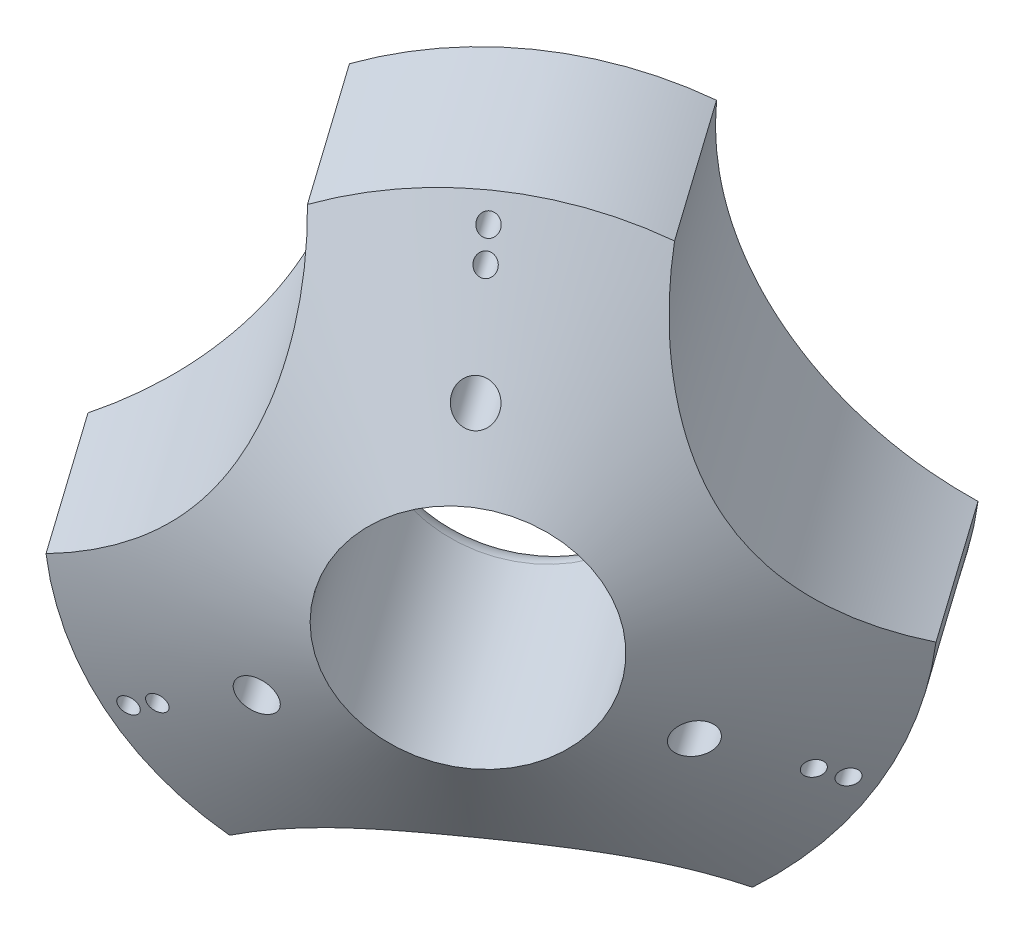
SolidWorks part; units mm, degrees
material "ABS"
ref_plane "前视基准面" through (0, 0, 0) normal (0, 0, 1) x (1, 0, 0)
ref_plane "上视基准面" through (0, 0, 0) normal (0, 1, 0) x (1, 0, 0)
ref_plane "右视基准面" through (0, 0, 0) normal (1, 0, 0) x (0, 0, -1)
other "Configuration Table"
sketch "草图1" plane through (0, 0, 0) normal (0, 1, 0) x (1, 0, 0)
  line L0 (0, 0) -> (50000, 0) construction
  line L1 (0, 0) -> (43301.2702, 25000) construction
  line L2 (0, 0) -> (25000, 43301.2702) construction
  line L3 (0, 0) -> (0, 50000) construction
  line L4 (0, 0) -> (-25000, 43301.2702) construction
  line L5 (0, 0) -> (-43301.2702, 25000) construction
  line L6 (-19.2134, -33.2787) -> (-30.3426, -17.5183)
  line L7 (-30.3426, -17.5183) -> (-61.1307, -35.2938)
  line L8 (-61.1307, -35.2938) -> (-38.709, -67.046)
  line L9 (-38.709, -67.046) -> (-19.2134, -33.2787)
  line L10 (-53.3699, -46.2842) -> (-45.2012, -40.516) construction
  line L11 (-45.2012, -40.516) -> (-33.2023, -57.5081)
  line L12 (-45.2012, -40.516) -> (-52.4343, -30.2729)
  spline S0 degree 4 poles (4.5441, -13.9852) (5.069, -13.9115) (6.1117, -13.7144) (7.5966, -13.2868) (9.4525, -12.4738) (11.1485, -11.4611) (12.673, -10.2854) (14.0902, -8.9027) (15.2006, -7.528) (16.0517, -6.2294) (16.6357, -5.1571) (16.9969, -4.4036) (17.2795, -3.7437) (17.4701, -3.2541) (17.647, -2.7595) (17.7869, -2.3315) (17.8956, -1.9726) (17.9965, -1.6106) (18.0724, -1.3201) (18.1431, -1.0312) (18.201, -0.7763) (18.2495, -0.5466) (18.2961, -0.3139) (18.338, -0.0934) (18.3688, 0.0809) (18.404, 0.2961) (18.438, 0.517) (18.4698, 0.7375) (18.5019, 0.9839) (18.5336, 1.2626) (18.5616, 1.5443) (18.5855, 1.8273) (18.6051, 2.1103) (18.6204, 2.3933) (18.6344, 2.7473) (18.6427, 3.1726) (18.6402, 3.6687) (18.606, 4.6606) (18.4743, 6.0736) (18.1443, 7.891) (17.4882, 10.0676) (16.5951, 12.1579) (15.4804, 14.1385) (14.1536, 15.9992) (12.6297, 17.7192) (10.7951, 19.3989) (8.6272, 20.9716) (6.1287, 22.3558) (3.3088, 23.4722) (0.3713, 24.2251) (-2.6362, 24.611) (-5.6679, 24.6319) (-8.6804, 24.2953) (-11.6337, 23.6131) (-14.4905, 22.6011) (-17.8988, 20.9477) (-21.6682, 18.3857) (-25.4815, 14.66) (-28.8831, 9.6089) (-31.2279, 3.9916) (-32.5355, -2.3024) (-32.5832, -9.4982) (-30.886, -17.2942) (-27.0418, -25.1548) (-21.1423, -32.1629) (-13.78, -37.6027) (-5.394, -41.2569) (3.5764, -43.0207) (12.7127, -42.8868) (21.6333, -40.9289) (30.0036, -37.2857) (37.5425, -32.1439) (44.0239, -25.7248) (49.277, -18.2707) (53.1837, -10.0336) (55.6749, -1.2666) (56.7255, 7.7843) (56.3496, 16.8863) (54.5948, 25.8236) (51.5367, 34.4007) (47.2736, 42.4454) (41.6252, 50.2164) (33.2939, 58.6988) (21.6024, 66.7973) (6.2316, 72.9489) (-11.9297, 75.3897) (-30.1426, 73.5037) (-47.4501, 67.5662) (-63.0493, 58.0235) (-76.3038, 45.4399) (-86.7456, 30.4509) (-94.067, 13.7235) (-98.1075, -4.0757) (-98.837, -22.3066) (-96.337, -40.374) (-90.7813, -57.7411) (-82.4178, -73.9383) (-71.5503, -88.568) (-58.5225, -101.306) (-43.7037, -111.9004) (-27.476, -120.169) (-10.2235, -125.9948) (7.6766, -129.3207) (25.8616, -130.1437) (43.989, -128.5088) (59.522, -125.003) (72.4202, -120.5917) (82.8104, -116.0253) (90.8771, -111.8583) (98.6697, -107.1992) (106.1617, -102.071) (114.2246, -95.801) (122.6763, -88.2215) (131.2888, -79.1727) (139.0767, -69.4058) (144.8157, -60.9536) (149.48, -53.1674) (153.2371, -46.1706) (156.1751, -40.0285) (158.8259, -33.7588) (160.8418, -28.4575) (162.3378, -24.1741) (163.5443, -20.3917) (164.5049, -17.1274) (165.2564, -14.393) (165.828, -12.1982) (166.3703, -9.9944) (166.8184, -8.0627) (167.1848, -6.398) (167.4765, -5.0161) (167.7053, -3.8925) (167.892, -2.9476) (168.0629, -2.0497) (168.1956, -1.3461) (168.4043, -0.1916) (168.4882, 0.2863) (168.6688, 1.3366) (168.7622, 1.9047) (168.8711, 2.5704) (169.0198, 3.5044) (169.1948, 4.6573) (169.389, 6.0027) (169.5701, 7.3351) (169.7422, 8.6768) (169.9433, 10.3507) (170.1641, 12.3645) (170.391, 14.7154) (170.6086, 17.4069) (170.7844, 20.1009) (170.9186, 22.7976) (171.0111, 25.4959) (171.0621, 28.1953) (171.0718, 30.8952) (171.0401, 33.595) (170.9491, 36.9686) (170.6302, 43.7113) (169.6923, 53.7988) (167.722, 65.8035) (165.138, 76.2991) (163.208, 82.7681) (162.3863, 85.3399) knots 0 0 0 0 0 0.002183 0.004365 0.006343 0.00832 0.010298 0.012275 0.014479 0.01558 0.016682 0.0173 0.017918 0.018536 0.018845 0.019463 0.019772 0.020081 0.02039 0.020699 0.021008 0.021162 0.021317 0.021626 0.021918 0.022064 0.02221 0.022501 0.022793 0.023085 0.023377 0.023669 0.023961 0.024253 0.024544 0.025128 0.025712 0.026296 0.028631 0.030966 0.033302 0.035637 0.037972 0.040307 0.042695 0.045083 0.048197 0.05131 0.054424 0.057538 0.060652 0.063766 0.066879 0.069993 0.073107 0.07622 0.082448 0.088676 0.094903 0.10113 0.107357 0.114993 0.124334 0.133675 0.143016 0.152357 0.161699 0.17104 0.18038 0.189722 0.199063 0.208404 0.217745 0.227086 0.236427 0.245769 0.25511 0.264451 0.273792 0.283133 0.292474 0.301815 0.313225 0.331907 0.35059 0.369272 0.387954 0.406636 0.425318 0.444001 0.462683 0.481365 0.500047 0.518729 0.537412 0.556094 0.574776 0.593458 0.612141 0.630823 0.649505 0.668187 0.68687 0.705552 0.724234 0.742916 0.752258 0.761599 0.77094 0.780281 0.789622 0.798963 0.812975 0.826987 0.840998 0.85034 0.85501 0.864351 0.873692 0.878363 0.883033 0.887704 0.892374 0.89471 0.897045 0.89938 0.901716 0.904051 0.905219 0.906387 0.907554 0.908722 0.909306 0.90989 0.911057 0.912447 0.912794 0.913142 0.913837 0.915226 0.916616 0.918006 0.919396 0.920785 0.922175 0.924955 0.927734 0.930513 0.933293 0.936072 0.938852 0.941631 0.944411 0.94719 0.94997 0.955529 0.972205 0.988882 1 1 1 1 1 construction
  spline S1 degree 4 poles (18.3541, 0) (18.3651, 0.0621) (18.381, 0.1554) (18.404, 0.2961) (18.438, 0.517) (18.4698, 0.7375) (18.5019, 0.9839) (18.5336, 1.2626) (18.5616, 1.5443) (18.5855, 1.8273) (18.6051, 2.1103) (18.6204, 2.3933) (18.6344, 2.7473) (18.6427, 3.1726) (18.6402, 3.6687) (18.606, 4.6606) (18.4743, 6.0736) (18.1443, 7.891) (17.4882, 10.0676) (16.5951, 12.1579) (15.4804, 14.1385) (14.1536, 15.9992) (12.6297, 17.7192) (10.7951, 19.3989) (8.6272, 20.9716) (6.1287, 22.3558) (3.3088, 23.4722) (0.3713, 24.2251) (-2.6362, 24.611) (-5.6679, 24.6319) (-8.6804, 24.2953) (-11.6337, 23.6131) (-14.4905, 22.6011) (-17.8988, 20.9477) (-21.6682, 18.3857) (-25.4815, 14.66) (-28.8831, 9.6089) (-31.2279, 3.9916) (-32.5355, -2.3024) (-32.5832, -9.4982) (-30.886, -17.2942) (-27.0418, -25.1548) (-21.1423, -32.1629) (-13.78, -37.6027) (-5.394, -41.2569) (3.5764, -43.0207) (12.7127, -42.8868) (21.6333, -40.9289) (30.0036, -37.2857) (37.5425, -32.1439) (44.0239, -25.7248) (49.277, -18.2707) (53.1837, -10.0336) (55.6749, -1.2666) (56.7255, 7.7843) (56.3496, 16.8863) (54.5948, 25.8236) (51.5367, 34.4007) (47.2736, 42.4454) (41.6252, 50.2164) (33.2939, 58.6988) (21.6024, 66.7973) (6.2316, 72.9489) (-11.9297, 75.3897) (-30.1426, 73.5037) (-47.4501, 67.5662) (-63.0493, 58.0235) (-76.3038, 45.4399) (-86.7456, 30.4509) (-94.067, 13.7235) (-98.1075, -4.0757) (-98.837, -22.3066) (-96.337, -40.374) (-90.7813, -57.7411) (-82.4178, -73.9383) (-71.5503, -88.568) (-58.5225, -101.306) (-43.7037, -111.9004) (-27.476, -120.169) (-10.2235, -125.9948) (7.6766, -129.3207) (25.8616, -130.1437) (43.989, -128.5088) (59.522, -125.003) (72.4202, -120.5917) (82.8104, -116.0253) (90.8771, -111.8583) (98.6697, -107.1992) (106.1617, -102.071) (114.2246, -95.801) (122.6763, -88.2215) (131.2888, -79.1727) (139.0767, -69.4058) (144.8157, -60.9536) (149.48, -53.1674) (153.2371, -46.1706) (156.1751, -40.0285) (158.8259, -33.7588) (160.8418, -28.4575) (162.3378, -24.1741) (163.5443, -20.3917) (164.5049, -17.1274) (165.2564, -14.393) (165.828, -12.1982) (166.3703, -9.9944) (166.8184, -8.0627) (167.1848, -6.398) (167.4765, -5.0161) (167.7053, -3.8925) (167.892, -2.9476) (168.0629, -2.0497) (168.1956, -1.3461) (168.3264, -0.6223) (168.3933, -0.2484) (168.4372, 0) knots 0.021626 0.021626 0.021626 0.021626 0.021626 0.021918 0.022064 0.02221 0.022501 0.022793 0.023085 0.023377 0.023669 0.023961 0.024253 0.024544 0.025128 0.025712 0.026296 0.028631 0.030966 0.033302 0.035637 0.037972 0.040307 0.042695 0.045083 0.048197 0.05131 0.054424 0.057538 0.060652 0.063766 0.066879 0.069993 0.073107 0.07622 0.082448 0.088676 0.094903 0.10113 0.107357 0.114993 0.124334 0.133675 0.143016 0.152357 0.161699 0.17104 0.18038 0.189722 0.199063 0.208404 0.217745 0.227086 0.236427 0.245769 0.25511 0.264451 0.273792 0.283133 0.292474 0.301815 0.313225 0.331907 0.35059 0.369272 0.387954 0.406636 0.425318 0.444001 0.462683 0.481365 0.500047 0.518729 0.537412 0.556094 0.574776 0.593458 0.612141 0.630823 0.649505 0.668187 0.68687 0.705552 0.724234 0.742916 0.752258 0.761599 0.77094 0.780281 0.789622 0.798963 0.812975 0.826987 0.840998 0.85034 0.85501 0.864351 0.873692 0.878363 0.883033 0.887704 0.892374 0.89471 0.897045 0.89938 0.901716 0.904051 0.905219 0.906387 0.907554 0.908722 0.909306 0.90989 0.911057 0.911057 0.911057 0.911057 0.911057
  spline S2 degree 4 poles (26.7771, -19.4547) (27.2791, -18.9699) (28.2564, -17.9726) (29.6389, -16.3972) (31.5138, -13.8737) (32.9647, -11.4834) (34.0651, -9.2997) (34.8847, -7.3726) (35.3191, -6.2309) (35.6599, -5.2409) (35.9229, -4.4091) (36.0959, -3.8235) (36.2363, -3.3192) (36.3702, -2.8132) (36.4765, -2.3905) (36.5777, -1.9654) (36.6735, -1.5395) (36.7371, -1.2443) (36.7899, -0.9895) (36.8338, -0.7701) (36.8689, -0.5895) (36.9122, -0.3614) (36.9643, -0.079) (37.0022, 0.137) (37.056, 0.4587) (37.1012, 0.7414) (37.1347, 0.96) (37.1737, 1.2255) (37.2176, 1.5413) (37.2661, 1.9157) (37.3168, 2.3441) (37.3624, 2.7721) (37.4134, 3.3079) (37.4649, 3.9519) (37.524, 4.9191) (37.5642, 6.2107) (37.5499, 8.58) (37.2749, 12.0191) (36.4953, 16.2666) (34.9181, 21.2024) (32.7382, 25.9024) (30.2297, 29.9345) (27.5748, 33.3344) (24.3272, 36.7897) (20.4102, 40.1789) (15.3713, 43.5302) (9.113, 46.471) (2.4988, 48.4837) (-3.4771, 49.4179) (-8.6498, 49.6296) (-15.5372, 49.2939) (-22.3494, 48.0444) (-29.7217, 45.4984) (-37.3047, 41.3681) (-42.9225, 37.3494) (-49.2948, 31.5248) (-55.7813, 23.4083) (-61.4472, 12.6507) (-65.4181, -1.9048) (-66.0143, -20.496) (-61.2011, -38.6277) (-51.6663, -54.6681) (-39.5267, -67.0168) (-28.241, -75.0457) (-15.7631, -81.0448) (-2.4709, -84.9081) (11.2641, -86.5959) (25.0917, -86.1269) (38.6859, -83.5703) (51.7521, -79.0376) (62.4941, -73.4702) (71.0671, -67.6624) (77.7289, -62.1925) (82.7475, -57.4634) (87.4361, -52.4071) (91.7776, -47.05) (95.7571, -41.4189) (99.3618, -35.5409) (102.1786, -30.2056) (104.3465, -25.5122) (105.8226, -21.9278) (106.7439, -19.5134) (107.4694, -17.486) (108.0246, -15.8552) (108.5543, -14.216) (109.0585, -12.5687) (109.5372, -10.914) (109.9904, -9.2519) (110.418, -7.5833) (110.7697, -6.1172) (111.0551, -4.8577) (111.2824, -3.8044) (111.4574, -2.9629) (111.6056, -2.2213) (111.7181, -1.6396) (111.7961, -1.2276) (111.8764, -0.7956) (111.9824, -0.2107) (112.0406, 0.1173) (112.149, 0.7476) (112.2197, 1.1704) (112.2736, 1.499) (112.3401, 1.912) (112.4454, 2.5814) (112.5829, 3.4978) (112.7468, 4.6683) (112.9181, 6.007) (113.1127, 7.6834) (113.3147, 9.6981) (113.5046, 12.0531) (113.6588, 14.7487) (113.7504, 17.4473) (113.7796, 20.1472) (113.7303, 24.197) (113.4243, 30.2662) (112.8255, 35.6383) (112.057, 40.3021) (111.5392, 42.9519) knots 0 0 0 0 0 0.005611 0.011222 0.016833 0.02525 0.028055 0.030861 0.033666 0.035069 0.036472 0.037875 0.038576 0.039277 0.04068 0.041381 0.042083 0.042784 0.043135 0.043486 0.043836 0.044187 0.044888 0.045754 0.046187 0.04662 0.047052 0.047485 0.048351 0.049216 0.050082 0.050948 0.051813 0.053545 0.055276 0.058738 0.062201 0.072588 0.082976 0.093363 0.103751 0.114138 0.121063 0.127988 0.141838 0.155688 0.169538 0.183388 0.197238 0.204163 0.211088 0.238788 0.252638 0.266488 0.280339 0.294189 0.321888 0.349589 0.377289 0.414571 0.469971 0.497671 0.525371 0.553071 0.580771 0.608471 0.636171 0.663871 0.691571 0.719271 0.746971 0.760821 0.774671 0.788521 0.802371 0.816222 0.830072 0.843922 0.857772 0.864697 0.871622 0.875084 0.878547 0.882009 0.885472 0.888934 0.892397 0.895859 0.899322 0.902784 0.904515 0.906247 0.907978 0.909709 0.910575 0.911008 0.91144 0.913172 0.914528 0.915207 0.915885 0.916563 0.917242 0.918599 0.921312 0.924025 0.926739 0.929452 0.934879 0.940306 0.945732 0.951159 0.956586 0.962013 0.978293 1 1 1 1 1 construction
  spline S3 degree 4 poles (36.9778, 0) (36.994, 0.0921) (37.0177, 0.2297) (37.056, 0.4587) (37.1012, 0.7414) (37.1347, 0.96) (37.1737, 1.2255) (37.2176, 1.5413) (37.2661, 1.9157) (37.3168, 2.3441) (37.3624, 2.7721) (37.4134, 3.3079) (37.4649, 3.9519) (37.524, 4.9191) (37.5642, 6.2107) (37.5499, 8.58) (37.2749, 12.0191) (36.4953, 16.2666) (34.9181, 21.2024) (32.7382, 25.9024) (30.2297, 29.9345) (27.5748, 33.3344) (24.3272, 36.7897) (20.4102, 40.1789) (15.3713, 43.5302) (9.113, 46.471) (2.4988, 48.4837) (-3.4771, 49.4179) (-8.6498, 49.6296) (-15.5372, 49.2939) (-22.3494, 48.0444) (-29.7217, 45.4984) (-37.3047, 41.3681) (-42.9225, 37.3494) (-49.2948, 31.5248) (-55.7813, 23.4083) (-61.4472, 12.6507) (-65.4181, -1.9048) (-66.0143, -20.496) (-61.2011, -38.6277) (-51.6663, -54.6681) (-39.5267, -67.0168) (-28.241, -75.0457) (-15.7631, -81.0448) (-2.4709, -84.9081) (11.2641, -86.5959) (25.0917, -86.1269) (38.6859, -83.5703) (51.7521, -79.0376) (62.4941, -73.4702) (71.0671, -67.6624) (77.7289, -62.1925) (82.7475, -57.4634) (87.4361, -52.4071) (91.7776, -47.05) (95.7571, -41.4189) (99.3618, -35.5409) (102.1786, -30.2056) (104.3465, -25.5122) (105.8226, -21.9278) (106.7439, -19.5134) (107.4694, -17.486) (108.0246, -15.8552) (108.5543, -14.216) (109.0585, -12.5687) (109.5372, -10.914) (109.9904, -9.2519) (110.418, -7.5833) (110.7697, -6.1172) (111.0551, -4.8577) (111.2824, -3.8044) (111.4574, -2.9629) (111.6056, -2.2213) (111.7181, -1.6396) (111.7961, -1.2276) (111.8764, -0.7956) (111.946, -0.4114) (111.9868, -0.1841) (112.0193, 0) knots 0.044888 0.044888 0.044888 0.044888 0.044888 0.045754 0.046187 0.04662 0.047052 0.047485 0.048351 0.049216 0.050082 0.050948 0.051813 0.053545 0.055276 0.058738 0.062201 0.072588 0.082976 0.093363 0.103751 0.114138 0.121063 0.127988 0.141838 0.155688 0.169538 0.183388 0.197238 0.204163 0.211088 0.238788 0.252638 0.266488 0.280339 0.294189 0.321888 0.349589 0.377289 0.414571 0.469971 0.497671 0.525371 0.553071 0.580771 0.608471 0.636171 0.663871 0.691571 0.719271 0.746971 0.760821 0.774671 0.788521 0.802371 0.816222 0.830072 0.843922 0.857772 0.864697 0.871622 0.875084 0.878547 0.882009 0.885472 0.888934 0.892397 0.895859 0.899322 0.902784 0.904515 0.906247 0.907978 0.909709 0.910575 0.911008 0.91144 0.913172 0.913172 0.913172 0.913172 0.913172
  dimension "D1" = 10
revolve "旋转1" add sketch "草图1" angle 360 about L8 region at (-25.2111, 0, 25.667) region at (-34.8365, 0, 35.7133)
ref_plane "基准面1" through (-3.1821, 0, -4.5063) normal (-0.5768, 0, -0.8169) x (-0.8169, 0, 0.5768)
sketch "草图2" plane through (-3.1821, 0, -4.5063) normal (-0.5768, 0, -0.8169) x (-0.8169, 0, 0.5768)
  line L0 (70.2941, 35.4031) -> (70.2941, 32.9031)
  line L1 (70.2941, 0) -> (70.2941, 20) construction
  line L2 (70.2941, 20) -> (70.2941, 30)
  line L3 (70.2941, 0) -> (19.6434, 29.2432) construction
  circle A0 centre (70.2941, 0) radius 35.4031 construction
  circle A1 centre (70.2941, 32.9031) radius 1
  circle A2 centre (70.2941, 30) radius 1
  circle A3 centre (70.2941, 20) radius 2
  circle A4 centre (19.6434, 29.2432) radius 36.25
  circle A5 centre (120.9447, 29.2432) radius 36.25
  circle A6 centre (98.789, -16.4516) radius 1
  circle A7 centre (96.2748, -15) radius 1
  circle A8 centre (87.6146, -10) radius 2
  circle A9 centre (70.2941, -58.4863) radius 36.25
  circle A10 centre (41.7991, -16.4516) radius 1
  circle A11 centre (44.3133, -15) radius 1
  circle A12 centre (52.9735, -10) radius 2
  circle A13 centre (70.2941, 0) radius 12.5
  point P5 (70.2941, 0)
  dimension "D5" = 2
  dimension "D6" = 2
  dimension "D7" = 4
  dimension "D8" = 72.5
  dimension "D10" = 25
  dimension "D1" = 2.5
  dimension "D2" = 20
  dimension "D3" = 10
  dimension "D4" = 60
  dimension "D9" = 3
extrude "切除-拉伸1" cut sketch "草图2" against normal blind 45 contours A4 | A5 | A9 | A1 | A2 | L1 A3 L2 | L2 A3 L1 | A6 | A7 | A8 | A12 | A11 | A10 | A13 region at (-60.0417, 30.6871, 35.6449) region at (-61.7255, 21.3742, 36.8339) region at (-60.0417, 32.216, 35.6449) region at (-19.2281, 29.2432, 6.8246) region at (-101.9778, 29.2432, 65.2578) region at (-83.8795, -16.4516, 52.4778) region at (-81.8258, -15, 51.0276) region at (-74.7515, -10, 46.0321) region at (-60.603, -58.4863, 36.0412) region at (-37.3264, -16.4516, 19.6046) region at (-39.3801, -15, 21.0548) region at (-46.4544, -10, 26.0503) region at (-60.603, 0, 36.0412)
fillet "圆角1" radius 3.5 1 edges at (-50.2602, 0, 29.0177)
shell "抽壳1" thickness 2
